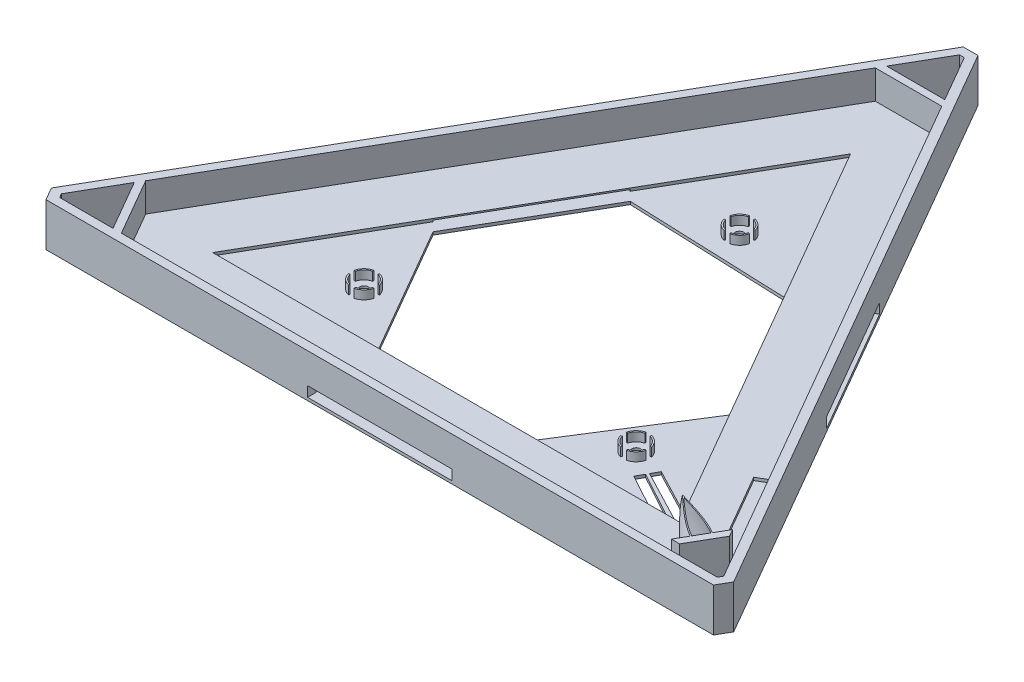
SolidWorks part; units mm, degrees
ref_plane "Front Plane" through (0, 0, 0) normal (0, 0, 1) x (1, 0, 0)
ref_plane "Top Plane" through (0, 0, 0) normal (0, 1, 0) x (1, 0, 0)
ref_plane "Right Plane" through (0, 0, 0) normal (1, 0, 0) x (0, 0, -1)
sketch "Sketch1" plane through (0, 0, 0) normal (0, 1, 0) x (1, 0, 0)
  line L0 (351.2729, 67.6655) -> (468.273, -134.9846)
  line L1 (347.2728, 67.6655) -> (347.2728, 65.1655) construction
  line L2 (409.773, -33.6595) -> (407.6079, -34.9095) construction
  line L3 (468.273, -134.9846) -> (464.2732, -141.9124)
  line L4 (230.2733, -141.9124) -> (464.2732, -141.9124)
  line L5 (230.2733, -141.9124) -> (226.2727, -134.9842)
  line L6 (226.2727, -134.9842) -> (343.2728, 67.6655)
  line L7 (353.4142, 63.9567) -> (351.2491, 62.7067) construction
  line L8 (347.2733, -141.9124) -> (347.2733, -139.4124) construction
  line L9 (231.7167, -139.4124) -> (462.8299, -139.4124)
  line L10 (284.7727, -33.6594) -> (286.9378, -34.9094) construction
  line L11 (344.7161, 65.1655) -> (349.8295, 65.1655)
  line L12 (465.3862, -134.9846) -> (349.8295, 65.1655)
  line L13 (466.2731, -138.4485) -> (464.1081, -137.1985) construction
  line L14 (462.8299, -139.4124) -> (465.3862, -134.9846)
  line L15 (229.1594, -134.9842) -> (344.7161, 65.1655)
  line L16 (229.1594, -134.9842) -> (231.7167, -139.4124)
  line L17 (286.9378, -34.9094) -> (287.3708, -35.1594) construction
  line L18 (230.438, -137.1983) -> (230.871, -136.9483) construction
  line L19 (232.0053, -138.9123) -> (229.7368, -134.9842)
  line L20 (343.2728, 67.6655) -> (351.2729, 67.6655)
  line L21 (345.0048, 64.6655) -> (229.7368, -134.9842)
  line L22 (349.5409, 64.6655) -> (345.0048, 64.6655)
  line L23 (249.0568, -126.4468) -> (246.8918, -127.697) construction
  line L24 (407.6079, -34.9095) -> (407.1749, -35.1595) construction
  line L26 (233.4463, -136.4089) -> (251.9226, -136.4093)
  line L27 (464.8089, -134.9846) -> (462.5412, -138.9123)
  line L28 (462.5412, -138.9123) -> (232.0053, -138.9123)
  line L29 (251.9226, -136.4093) -> (241.8609, -118.9847)
  line L30 (241.8609, -118.9847) -> (232.6236, -134.9842)
  line L31 (232.6236, -134.9842) -> (233.4463, -136.4089)
  line L33 (287.3708, -35.1594) -> (289.5359, -36.4094) construction
  line L34 (254.8093, -136.4089) -> (243.3042, -116.4848)
  line L35 (335.7675, 43.666) -> (243.3042, -116.4848)
  line L36 (358.7782, 43.666) -> (335.7675, 43.666)
  line L38 (289.5359, -36.4094) -> (306.8564, -46.4094) construction
  line L41 (461.939, -134.9846) -> (461.1164, -136.4093)
  line L42 (347.2688, -136.4172) -> (347.2688, -116.4172) construction
  line L43 (442.6021, -136.4093) -> (452.6999, -118.9847)
  line L44 (245.2636, -119.878) -> (249.0568, -126.4468) construction
  line L45 (452.6999, -118.9847) -> (461.939, -134.9846)
  line L48 (461.1164, -136.4093) -> (442.6021, -136.4093)
  line L49 (405.0134, -36.4027) -> (387.6936, -46.404) construction
  line L50 (439.7283, -128.9846) -> (405.0134, -128.9846)
  line L51 (357.3348, 46.166) -> (337.2109, 46.166)
  line L52 (337.2109, 46.166) -> (346.4484, 62.1659)
  line L53 (346.4484, 62.1659) -> (348.0966, 62.164)
  line L54 (348.0966, 62.164) -> (357.3348, 46.166)
  line L55 (228.273, -138.4483) -> (387.6936, -46.404) construction
  line L56 (347.2688, -116.4172) -> (347.2728, 43.666) construction
  line L57 (266.4391, -116.428) -> (428.1137, -116.4172)
  line L58 (347.2736, 23.6092) -> (428.1137, -116.4172)
  line L59 (266.4391, -116.428) -> (347.2736, 23.6092)
  line L60 (439.7283, -136.4254) -> (439.7283, -132.9254) construction
  line L61 (451.2487, -116.4715) -> (448.6507, -117.9717) construction
  line L62 (452.6999, -118.9847) -> (358.7782, 43.666)
  line L63 (442.6021, -136.4093) -> (254.8093, -136.4089)
  line L64 (441.749, -132.9254) -> (444.621, -132.9254)
  line L65 (448.6507, -117.9717) -> (450.9647, -121.979) construction
  line L66 (449.5167, -119.4714) -> (450.9647, -121.979)
  line L67 (441.749, -132.9254) -> (449.5167, -119.4714)
  line L68 (450.9647, -121.979) -> (444.621, -132.9254)
  line L69 (405.0134, -128.9846) -> (405.0134, -134.9846)
  line L70 (444.9234, -120.3654) -> (427.4553, -90.1147)
  line L73 (405.0134, -134.9846) -> (439.7283, -134.9846)
  line L76 (439.7283, -134.9846) -> (439.7283, -128.9846)
  line L77 (432.6513, -87.1143) -> (427.4553, -90.1147)
  line L78 (405.0134, -134.9846) -> (433.4739, -85.6896) construction
  line L81 (432.6513, -87.1143) -> (450.1194, -117.365)
  line L83 (450.1194, -117.365) -> (444.9234, -120.3654)
  point P13 (407.6079, -34.9095)
  point P20 (464.1081, -137.1985)
  point P23 (347.2733, -139.4124)
  point P25 (347.2732, -141.9124)
  point P27 (347.2728, 65.1655)
  point P31 (286.9378, -34.9094)
  point P37 (287.3708, -35.1594)
  point P39 (230.871, -136.9483)
  point P41 (347.2728, 64.6655)
  point P45 (407.1749, -35.1595)
  point P50 (246.8918, -127.697)
  point P56 (289.5359, -36.4094)
  point P58 (249.0568, -126.4468)
  point P60 (347.2728, 43.666)
  point P62 (345.0048, -136.4089)
  point P64 (445.4885, -126.4485)
  point P71 (447.651, -127.697)
  point P77 (347.2728, 46.166)
  point P84 (347.2688, -116.4172)
  point P87 (387.6936, -46.404)
  point P89 (306.8564, -46.4094)
  point P100 (405.0134, -36.4027)
  dimension "D1" = 2.5
  dimension "D2" = 2.5
  dimension "D3" = 2.5
  dimension "D4" = 2.5
  dimension "D5" = 2.5
  dimension "D6" = 2.5
  dimension "D7" = 0.5
  dimension "D8" = 0.5
  dimension "D9" = 0.5
  dimension "D10" = 2.5
  dimension "D11" = 2.5
  dimension "D12" = 20
  dimension "D13" = 20
  dimension "D14" = 20
  dimension "D15" = 3.5
  dimension "D16" = 3
  dimension "D17" = 6
  dimension "D18" = 6
  dimension "D19" = 234
extrude "Boss-Extrude1" add sketch "Sketch1" along normal blind 1 contours L36 L35 L34 L57 L59 L58 region at (251.4484, 0, 125.0658)
extrude "Boss-Extrude2" add sketch "Sketch1<9>" along normal blind 11 contours L28 L27 L22 L21 L19 L31 L30 L29 L26 L34 L35 L36 L41 L48 L43 L45 L53 L54 L51 L52 | L68 L64 L67 L66 region at (230.7087, 0, 137.042)
sketch "Sketch1<9>" plane through (0, 0, 0) normal (0, 1, 0) x (1, 0, 0) same geometry as "Sketch1"
extrude "Boss-Extrude3" add sketch "Sketch1<10>" along normal blind 5 and the other way blind 3 contours L28 L27 L22 L21 L19 L31 L30 L29 L26 L34 L35 L36 L41 L48 L43 L45 L53 L54 L51 L52 | L68 L64 L67 L66 region at (230.7087, 0, 137.042)
sketch "Sketch1<10>" plane through (0, 0, 0) normal (0, 1, 0) x (1, 0, 0) same geometry as "Sketch1"
sketch "Sketch3" plane through (290.5896, 0, -167.772) normal (0.866, 0, -0.5) x (-0.5, 0, -0.866)
  line L1 (-261.593, -6.5) -> (-211.593, -6.5)
  line L2 (-261.593, -6.5) -> (-261.593, 0.5)
  line L3 (-261.593, 0.5) -> (-211.593, 0.5)
  line L4 (-211.593, -6.5) -> (-211.593, 0.5)
  line L5 (-261.593, -6.5) -> (-211.593, 0.5) construction
  line L6 (-261.593, 0.5) -> (-211.593, -6.5) construction
  point P0 (-236.593, -3)
  dimension "D1" = 50
  dimension "D2" = 7
extrude "Cut-Extrude3" cut sketch "Sketch3" against normal blind 25
sketch "Sketch5" plane through (0, 0, 139.4124) normal (0, 0, 1) x (1, 0, 0)
  line L0 (231.7167, -3) -> (462.8299, -3) construction
  line L1 (322.2733, -6.5) -> (372.2733, -6.5)
  line L2 (322.2733, -6.5) -> (322.2733, 0.5)
  line L3 (322.2733, 0.5) -> (372.2733, 0.5)
  line L4 (372.2733, -6.5) -> (372.2733, 0.5)
  line L5 (322.2733, -6.5) -> (372.2733, 0.5) construction
  line L6 (322.2733, 0.5) -> (372.2733, -6.5) construction
  point P0 (347.2733, -3)
  dimension "D1" = 50
  dimension "D2" = 7
extrude "Cut-Extrude4" cut sketch "Sketch5" against normal blind 25
sketch "Sketch6" plane through (230.3194, 0, 132.9752) normal (-0.866, 0, -0.5) x (-0.5, 0, 0.866)
  line L0 (2.3199, -3) -> (-228.7932, -3) construction
  line L1 (-138.2367, -6.5) -> (-88.2367, -6.5)
  line L2 (-138.2367, -6.5) -> (-138.2367, 0.5)
  line L3 (-138.2367, 0.5) -> (-88.2367, 0.5)
  line L4 (-88.2367, -6.5) -> (-88.2367, 0.5)
  line L5 (-138.2367, -6.5) -> (-88.2367, 0.5) construction
  line L6 (-138.2367, 0.5) -> (-88.2367, -6.5) construction
  point P0 (-113.2367, -3)
  dimension "D1" = 50
  dimension "D2" = 7
extrude "Cut-Extrude5" cut sketch "Sketch6" against normal blind 25
sketch "Sketch8" plane through (0, -3, 0) normal (0, -1, 0) x (1, 0, 0)
  line L1 (349.8295, -65.1655) -> (465.3862, 134.9846)
  line L2 (465.3862, 134.9846) -> (462.8299, 139.4124)
  line L4 (444.621, 132.9254) -> (450.9647, 121.979)
  line L6 (462.8299, 139.4124) -> (231.7167, 139.4124)
  line L9 (452.6999, 118.9847) -> (461.939, 134.9846)
  line L12 (461.939, 134.9846) -> (461.1164, 136.4093)
  line L15 (450.9647, 121.979) -> (444.621, 132.9254) construction
  line L17 (461.1164, 136.4093) -> (442.6021, 136.4093)
  line L19 (322.2733, 116.4243) -> (294.3582, 68.0611)
  line L20 (294.3582, 68.0611) -> (319.3545, 24.7577)
  line L21 (319.3545, 24.7577) -> (376.4737, 26.9694)
  line L22 (376.4737, 26.9694) -> (401.4727, 70.2712)
  line L23 (401.4727, 70.2712) -> (372.2733, 116.4209)
  line L24 (372.2733, 116.4209) -> (322.2733, 116.4243)
  line L25 (386.873, 93.3461) -> (395.3235, 98.6928) construction
  line L30 (308.3157, 92.2427) -> (299.6549, 97.2417) construction
  line L31 (347.9141, 25.8635) -> (348.3013, 15.8635) construction
  line L37 (231.7167, 139.4124) -> (229.1594, 134.9842)
  line L39 (233.4463, 136.4089) -> (251.9226, 136.4093)
  line L40 (251.9226, 136.4093) -> (241.8609, 118.9847)
  line L41 (241.8609, 118.9847) -> (232.6236, 134.9842)
  line L42 (232.6236, 134.9842) -> (233.4463, 136.4089)
  line L43 (349.8295, -65.1655) -> (344.7161, -65.1655)
  line L44 (344.7161, -65.1655) -> (229.1594, 134.9842)
  line L45 (337.2109, -46.166) -> (357.3348, -46.166)
  line L46 (357.3348, -46.166) -> (348.0966, -62.164)
  line L47 (348.0966, -62.164) -> (346.4484, -62.1659)
  line L48 (346.4484, -62.1659) -> (337.2109, -46.166)
  line L53 (442.6021, 136.4093) -> (439.0196, 136.4093)
  line L54 (439.0196, 136.4093) -> (420.3794, 116.4177)
  line L55 (424.5493, 110.2432) -> (451.8713, 117.5496)
  line L59 (372.2733, 116.4209) -> (428.1137, 116.4172) construction
  line L60 (401.4727, 70.2712) -> (428.1137, 116.4172) construction
  line L61 (451.8713, 117.5496) -> (452.6999, 118.9847)
  line L62 (426.6202, 116.4173) -> (441.749, 132.9254)
  line L63 (441.749, 132.9254) -> (444.621, 132.9254)
  line L65 (427.3476, 115.0902) -> (449.5167, 119.4714)
  line L66 (449.5167, 119.4714) -> (450.9647, 121.979)
  line L67 (449.5167, 119.4714) -> (450.9647, 121.979) construction
  line L68 (441.749, 132.9254) -> (449.5167, 119.4714) construction
  line L70 (403.8523, 103.9378) -> (426.6202, 116.4173)
  line L72 (404.333, 103.0609) -> (427.3476, 115.0902)
  line L74 (442.6021, 136.4093) -> (372.2733, 136.4092) construction
  line L75 (461.939, 134.9846) -> (418.7954, 60.2699) construction
  line L76 (420.3794, 116.4177) -> (402.4104, 106.5685)
  line L77 (402.4104, 106.5685) -> (403.8523, 103.9378)
  line L78 (404.333, 103.0609) -> (405.7749, 100.4301)
  line L79 (405.7749, 100.4301) -> (424.5493, 110.2432)
  line L80 (395.3235, 98.6928) -> (447.7929, 127.4522) construction
  line L81 (395.3235, 98.6928) -> (404.0927, 103.4993) construction
  line L82 (404.0927, 103.4993) -> (404.333, 103.0609) construction
  line L83 (404.0927, 103.4993) -> (403.8523, 103.9378) construction
  line L84 (403.8523, 103.9378) -> (402.4104, 106.5685) construction
  line L85 (404.333, 103.0609) -> (405.7749, 100.4301) construction
  line L86 (402.4104, 106.5685) -> (420.3794, 116.4177) construction
  line L87 (405.7749, 100.4301) -> (424.5493, 110.2432) construction
  line L88 (404.333, 103.0609) -> (427.842, 115.9466) construction
  line L89 (403.8523, 103.9378) -> (426.6202, 116.4173) construction
  line L90 (426.6202, 116.4173) -> (427.3476, 115.0902) construction
  line L91 (420.3794, 116.4177) -> (424.1464, 109.5452) construction
  circle A0 centre (395.3235, 98.6928) radius 1.5
  circle A1 centre (348.3013, 15.8635) radius 1.5
  circle A2 centre (299.6549, 97.2417) radius 1.5
  dimension "D6" = 3
  dimension "D7" = 3
  dimension "D8" = 3
  dimension "D1" = 10
  dimension "D2" = 0.5
  dimension "D3" = 10
  dimension "D4" = 10
  dimension "D5" = 10
  dimension "D9" = 0.5
  dimension "D10" = 3
  dimension "D11" = 3
extrude "Boss-Extrude5" add sketch "Sketch8" along normal blind 1
sketch "Sketch12" plane through (0, -3, 0) normal (0, 1, 0) x (1, 0, 0)
  line L0 (348.3013, -11.8635) -> (348.3013, -11.3635) construction
  line L1 (348.3013, -11.3635) -> (349.2951, -11.4746) construction
  line L2 (349.2951, -11.4746) -> (349.1847, -11.9623)
  line L3 (348.3013, -11.3635) -> (347.3075, -11.4746) construction
  line L4 (347.3075, -11.4746) -> (347.4179, -11.9623)
  line L5 (352.3013, -15.8635) -> (352.8013, -15.8635) construction
  line L6 (344.3013, -15.8635) -> (343.8013, -15.8635) construction
  line L7 (348.3013, -19.8635) -> (348.3013, -20.3635) construction
  line L8 (352.8013, -15.8635) -> (352.6902, -14.8697) construction
  line L9 (352.8013, -15.8635) -> (352.6902, -16.8573) construction
  line L10 (343.8013, -15.8635) -> (343.9124, -14.8697) construction
  line L11 (343.8013, -15.8635) -> (343.9124, -16.8573) construction
  line L12 (348.3013, -20.3635) -> (349.2951, -20.2524) construction
  line L13 (348.3013, -20.3635) -> (347.3075, -20.2524) construction
  line L14 (343.9124, -14.8697) -> (348.3013, -15.8635) construction
  line L15 (348.3013, -15.8635) -> (352.6902, -14.8697) construction
  line L16 (343.9124, -16.8573) -> (348.3013, -15.8635) construction
  line L17 (348.3013, -15.8635) -> (352.6902, -16.8573) construction
  line L18 (347.3075, -20.2524) -> (348.3013, -15.8635) construction
  line L19 (348.3013, -15.8635) -> (349.2951, -20.2524) construction
  line L20 (343.9124, -14.8697) -> (344.4001, -14.9801)
  line L21 (343.9124, -16.8573) -> (344.4001, -16.7469)
  line L22 (347.3075, -20.2524) -> (347.4179, -19.7648)
  line L23 (349.2951, -20.2524) -> (349.1847, -19.7648)
  line L24 (352.6902, -14.8697) -> (352.2025, -14.9801)
  line L25 (352.6902, -16.8573) -> (352.2025, -16.7469)
  line L26 (395.3235, -94.1928) -> (395.3235, -98.6928) construction
  line L27 (395.3235, -98.6928) -> (390.8235, -98.6928) construction
  line L28 (390.8235, -98.6928) -> (390.9347, -97.699) construction
  line L29 (399.8235, -98.6928) -> (395.3235, -98.6928) construction
  line L30 (395.3235, -98.6928) -> (395.3235, -103.1928) construction
  line L31 (395.3235, -103.1928) -> (396.3173, -103.0817) construction
  line L32 (395.3235, -94.1928) -> (396.3173, -94.3039) construction
  line L33 (395.3235, -94.1928) -> (394.3297, -94.3039) construction
  line L34 (399.7124, -97.699) -> (399.8235, -98.6928) construction
  line L35 (399.8235, -98.6928) -> (399.7124, -99.6866) construction
  line L36 (390.9347, -99.6866) -> (390.8235, -98.6928) construction
  line L37 (394.3297, -103.0817) -> (395.3235, -103.1928) construction
  line L38 (394.3297, -94.3039) -> (395.3235, -98.6928) construction
  line L39 (395.3235, -98.6928) -> (396.3173, -94.3039) construction
  line L40 (390.9347, -99.6866) -> (395.3235, -98.6928) construction
  line L41 (395.3235, -98.6928) -> (390.9347, -97.699) construction
  line L42 (399.7124, -97.699) -> (395.3235, -98.6928) construction
  line L43 (395.3235, -98.6928) -> (399.7124, -99.6866) construction
  line L44 (394.3297, -103.0817) -> (395.3235, -98.6928) construction
  line L45 (395.3235, -98.6928) -> (396.3173, -103.0817) construction
  line L46 (394.3297, -94.3039) -> (394.4402, -94.7916)
  line L47 (396.3173, -94.3039) -> (396.2069, -94.7916)
  line L48 (399.7124, -97.699) -> (399.2248, -97.8094)
  line L49 (399.7124, -99.6866) -> (399.2248, -99.5762)
  line L50 (396.3173, -103.0817) -> (396.2069, -102.5941)
  line L51 (394.3297, -103.0817) -> (394.4402, -102.5941)
  line L52 (390.9347, -99.6866) -> (391.4223, -99.5762)
  line L53 (390.9347, -97.699) -> (391.4248, -97.7985)
  line L54 (299.6549, -92.7417) -> (299.6549, -97.2417) construction
  line L55 (299.6549, -97.2417) -> (304.1549, -97.2417) construction
  line L56 (299.6549, -101.7417) -> (299.6549, -97.2417) construction
  line L57 (299.6549, -97.2417) -> (295.1549, -97.2417) construction
  line L58 (299.6549, -97.2417) -> (298.6611, -92.8528) construction
  line L59 (298.6611, -92.8528) -> (299.6549, -92.7417) construction
  line L60 (299.6549, -92.7417) -> (300.6487, -92.8528) construction
  line L61 (300.6487, -92.8528) -> (299.6549, -97.2417) construction
  line L62 (299.6549, -97.2417) -> (304.0438, -96.2479) construction
  line L63 (304.0438, -96.2479) -> (304.1549, -97.2417) construction
  line L64 (304.1549, -97.2417) -> (304.0438, -98.2355) construction
  line L65 (304.0438, -98.2355) -> (299.6549, -97.2417) construction
  line L66 (299.6549, -97.2417) -> (300.6487, -101.6306) construction
  line L67 (300.6487, -101.6306) -> (299.6549, -101.7417) construction
  line L68 (299.6549, -101.7417) -> (298.6611, -101.6306) construction
  line L69 (298.6611, -101.6306) -> (299.6549, -97.2417) construction
  line L70 (299.6549, -97.2417) -> (295.266, -98.2355) construction
  line L71 (295.266, -98.2355) -> (295.1549, -97.2417) construction
  line L72 (295.1549, -97.2417) -> (295.266, -96.2479) construction
  line L73 (295.266, -96.2479) -> (299.6549, -97.2417) construction
  line L74 (295.266, -96.2479) -> (295.7537, -96.3583)
  line L75 (295.266, -98.2355) -> (295.7537, -98.1251)
  line L76 (298.6611, -101.6306) -> (298.7715, -101.1429)
  line L77 (300.6487, -101.6306) -> (300.5383, -101.1429)
  line L78 (304.0438, -98.2355) -> (303.5561, -98.1251)
  line L79 (304.0438, -96.2479) -> (303.5561, -96.3583)
  line L80 (300.6487, -92.8528) -> (300.5383, -93.3404)
  line L81 (298.6611, -92.8528) -> (298.7715, -93.3404)
  circle A0 centre (348.3013, -15.8635) radius 4.5
  circle A1 centre (395.3235, -98.6928) radius 4.5
  circle A2 centre (299.6549, -97.2417) radius 4.5
  circle A3 centre (348.3013, -15.8635) radius 4
  circle A4 centre (395.3235, -98.6928) radius 4
  circle A5 centre (299.6549, -97.2417) radius 4
  dimension "D1" = 9
  dimension "D2" = 9
  dimension "D3" = 9
  dimension "D4" = 8
  dimension "D5" = 8
  dimension "D6" = 8
  dimension "D7" = 1
  dimension "D8" = 1
  dimension "D9" = 1
  dimension "D10" = 1
  dimension "D11" = 1
  dimension "D12" = 1
  dimension "D13" = 1
  dimension "D14" = 1
  dimension "D15" = 1
  dimension "D16" = 1
  dimension "D17" = 1
  dimension "D18" = 1
  dimension "D19" = 1
  dimension "D20" = 1
  dimension "D21" = 1
  dimension "D22" = 1
  dimension "D23" = 1
  dimension "D24" = 1
  dimension "D25" = 1
  dimension "D26" = 1
  dimension "D27" = 1
  dimension "D28" = 1
  dimension "D29" = 1
  dimension "D30" = 1
extrude "Boss-Extrude10" add sketch "Sketch12" along normal blind 3 contours A3 L4 A0 L20 | A3 L24 A0 L2 | A3 L23 A0 L25 | A3 L21 A0 L22 | A4 L46 A1 L53 | A4 L48 A1 L47 | A4 L50 A1 L49 | A4 L52 A1 L51 | A5 L81 A2 L74 | A5 L79 A2 L80 | A5 L77 A2 L78 | A5 L75 A2 L76 region at (351.1537, -3, 13.0111) region at (345.4489, -3, 13.0111) region at (351.1537, -3, 18.7159) region at (345.4489, -3, 18.7159) region at (392.4726, -3, 95.8382) region at (398.1759, -3, 95.8404) region at (392.4712, -3, 101.5452) region at (398.1759, -3, 101.5452) region at (296.8025, -3, 94.3893) region at (296.8025, -3, 100.0941) region at (302.5073, -3, 94.3893) region at (302.5073, -3, 100.0941)
sketch "Sketch13" plane through (0, 1, 0) normal (0, 1, 0) x (1, 0, 0)
  line L0 (428.1137, -116.4172) -> (450.9647, -121.979) construction
  line L1 (428.1137, -116.4172) -> (444.621, -132.9254) construction
  line L2 (428.1137, -116.4172) -> (448.4258, -121.361)
  line L3 (428.1137, -116.4172) -> (442.8003, -131.1046)
  line L4 (441.749, -132.9254) -> (449.5167, -119.4714) construction
  line L5 (442.8003, -131.1046) -> (448.4258, -121.361)
  line L6 (428.1137, -116.4172) -> (445.613, -126.2328) construction
  line L7 (428.1137, -116.4172) -> (445.557, -126.2014) construction
  line L8 (445.557, -126.2014) -> (448.1758, -121.794)
  line L9 (441.749, -132.9254) -> (449.5167, -119.4714) construction
  line L10 (445.557, -126.2014) -> (443.0503, -130.6716)
  line L11 (443.0503, -130.6716) -> (448.1758, -121.794)
  line L12 (448.1758, -121.794) -> (428.9858, -116.9064)
  line L13 (428.9858, -116.9064) -> (443.0503, -130.6716)
  dimension "D1" = 20
  dimension "D2" = 0.5
  dimension "D3" = 0.5
  dimension "D4" = 1
revolve "Revolve1" add sketch "Sketch13" angle 90 about L5 region at (438.2104, 1, 119.1326)
sketch "Sketch15" plane through (388.8702, 0, 224.5143) normal (0.866, 0, 0.5) x (0.5, 0, -0.866)
  line L1 (110.54, 11) -> (118.4142, 11)
  line L2 (110.54, 11) -> (110.54, 23.308)
  line L3 (110.54, 23.308) -> (118.4142, 23.308)
  line L4 (118.4142, 11) -> (118.4142, 23.308)
extrude "Cut-Extrude7" cut sketch "Sketch15" against normal blind 38
